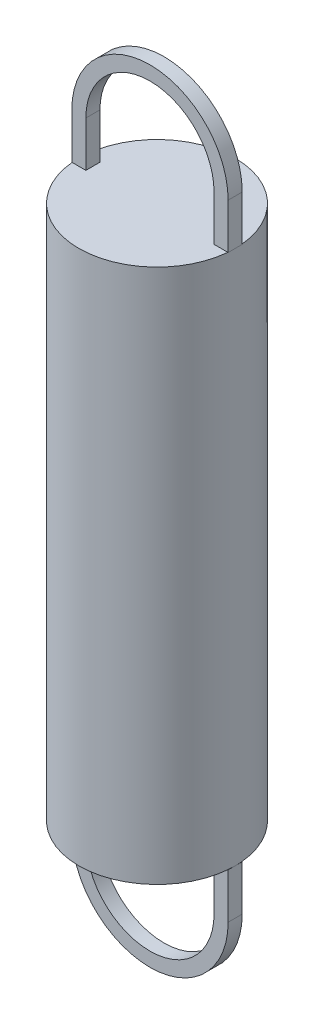
SolidWorks part; units mm, degrees
ref_plane "Plan de face" through (0, 0, 0) normal (0, 0, 1) x (1, 0, 0)
ref_plane "Plan de dessus" through (0, 0, 0) normal (0, 1, 0) x (1, 0, 0)
ref_plane "Plan de droite" through (0, 0, 0) normal (1, 0, 0) x (0, 0, -1)
sketch "Esquisse8" plane through (0, 0, 0) normal (0, 0, 1) x (1, 0, 0)
  line L0 (-2.5, 10) -> (2.5, 10) construction
  line L1 (-2.5, 10) -> (-2.5, 8.55)
  line L2 (2.5, 10) -> (2.5, 8.55)
  line L4 (0, 0) -> (4.2742, 0) construction
  line L8 (-2.05, 10) -> (-2.05, 8.55)
  line L9 (2.05, 10) -> (2.05, 8.55)
  line L14 (2.05, -10) -> (2.05, -8.55)
  line L15 (-2.05, -10) -> (-2.05, -8.55)
  line L16 (2.5, -10) -> (2.5, -8.55)
  line L17 (-2.5, -10) -> (-2.5, -8.55)
  line L18 (0, 8.55) -> (0, -8.55)
  line L19 (-2.5, -8.55) -> (2.5, -8.55)
  line L20 (-2.5, -8.55) -> (-2.5, 8.55)
  line L21 (-2.5, 8.55) -> (2.5, 8.55)
  line L22 (2.5, -8.55) -> (2.5, 8.55)
  arc A0 (-2.5, 10) -> (2.5, 10) centre (0, 10) cw
  arc A2 (-2.05, 10) -> (2.05, 10) centre (0, 10) cw
  arc A3 (-2.05, -10) -> (2.05, -10) centre (0, -10) ccw
  arc A4 (-2.5, -10) -> (2.5, -10) centre (0, -10) ccw
  point P5 (0, 10)
  point P15 (0, -12.5)
  point P17 (0, 12.5)
  dimension "D1" = 25
  dimension "D3" = 3.95
  dimension "D2" = 0.45
revolve "Révolution2" add sketch "Esquisse8" angle 360 about L18 region at (-1.25, 0, 0)
extrude "Boss.-Extru.1" add sketch "Esquisse8<4>" along normal mid plane 0.45 contours L17 A4 L16 L19 L14 A3 L15 | L8 A2 L9 L21 L2 A0 L1 region at (0, 12.4363, 0) region at (-2.275, -8.6137, 0)
sketch "Esquisse8<4>" plane through (0, 0, 0) normal (0, 0, 1) x (1, 0, 0) same geometry as "Esquisse8"
